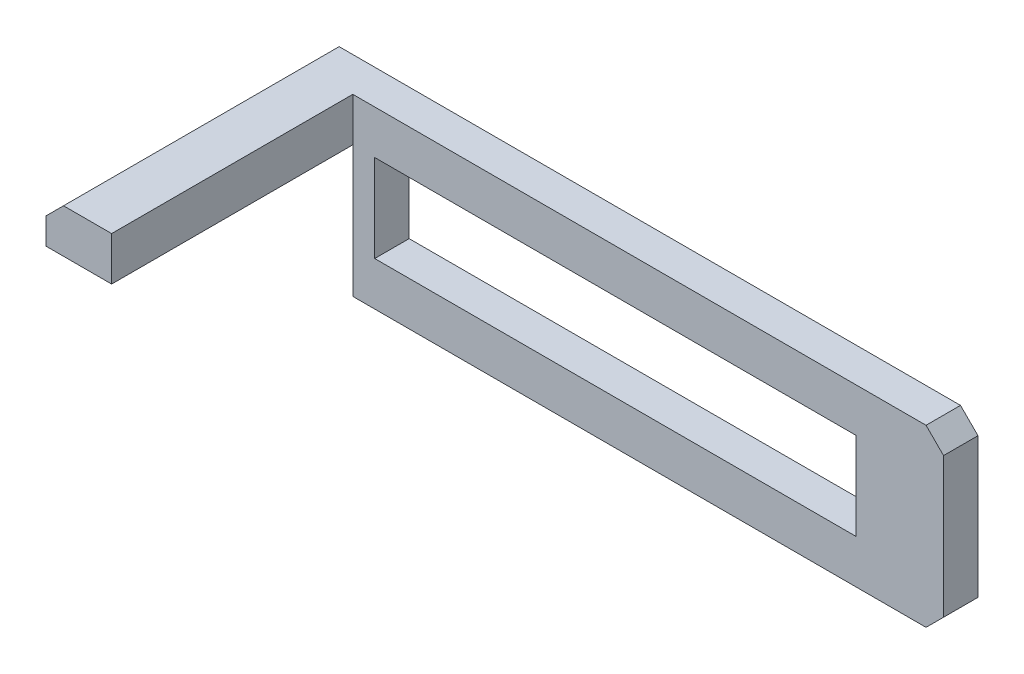
SolidWorks part; units mm, degrees
ref_plane "Front Plane" through (0, 0, 0) normal (0, 0, 1) x (1, 0, 0)
ref_plane "Top Plane" through (0, 0, 0) normal (0, 1, 0) x (1, 0, 0)
ref_plane "Right Plane" through (0, 0, 0) normal (1, 0, 0) x (0, 0, -1)
sketch "Sketch1" plane through (0, 0, 0) normal (0, 0, 1) x (1, 0, 0)
  line L1 (0, 0) -> (-95.25, 0)
  line L2 (0, 0) -> (0, 25.4)
  line L3 (0, 25.4) -> (-95.25, 25.4)
  line L4 (-95.25, 0) -> (-95.25, 25.4)
  line L5 (-12.7, 19.05) -> (-82.55, 19.05)
  line L6 (-12.7, 19.05) -> (-12.7, 6.35)
  line L7 (-12.7, 6.35) -> (-82.55, 6.35)
  line L8 (-82.55, 19.05) -> (-82.55, 6.35)
  point P9 (-47.625, 25.4)
  point P10 (-47.625, 6.35)
  point P11 (0, 0)
  point P12 (-12.7, 19.05)
  point P13 (-12.7, 12.7)
  dimension "D1" = 95.25
  dimension "D2" = 25.4
  dimension "D3" = 6.35
  dimension "D4" = 12.7
  dimension "D5" = 6.35
extrude "Boss-Extrude1" add sketch "Sketch1" along normal blind 5 contours L8 L3 L4 L1 L2 L6 L7 region at (-47.625, 0.9858, 0)
sketch "Sketch2" plane through (0, 0, 5) normal (0, 0, 1) x (1, 0, 0)
  line L0 (0, 0) -> (-95.25, 0) construction
  line L1 (-95.25, 19.05) -> (-85.725, 19.05)
  line L2 (-95.25, 19.05) -> (-95.25, 25.4)
  line L3 (-95.25, 25.4) -> (-85.725, 25.4)
  line L4 (-85.725, 19.05) -> (-85.725, 25.4)
  line L5 (-95.25, 0) -> (-95.25, 25.4) construction
  dimension "D1" = 9.525
  dimension "D2" = 6.35
  dimension "D3" = 19.05
extrude "Boss-Extrude2" add sketch "Sketch2" along normal blind 35
chamfer "Chamfer1" distance 2.54 angle 45 4 edges at (0, 0, 2.5) (-95.25, 0, 2.5) (0, 25.4, 2.5) (-95.25, 25.4, 20)
sketch "Sketch4" plane through (0, 0, 5) normal (0, 0, 1) x (1, 0, 0)
  line L0 (-95.25, 2.54) -> (-95.25, 19.05) construction
  line L1 (-85.725, 19.05) -> (-95.25, 19.05)
  line L2 (-85.725, 19.05) -> (-85.725, 0)
  line L3 (-85.725, 0) -> (-95.25, 0)
  line L4 (-95.25, 19.05) -> (-95.25, 0)
  line L5 (-2.54, 0) -> (-92.71, 0) construction
extrude "Cut-Extrude2" cut sketch "Sketch4" against normal through all
